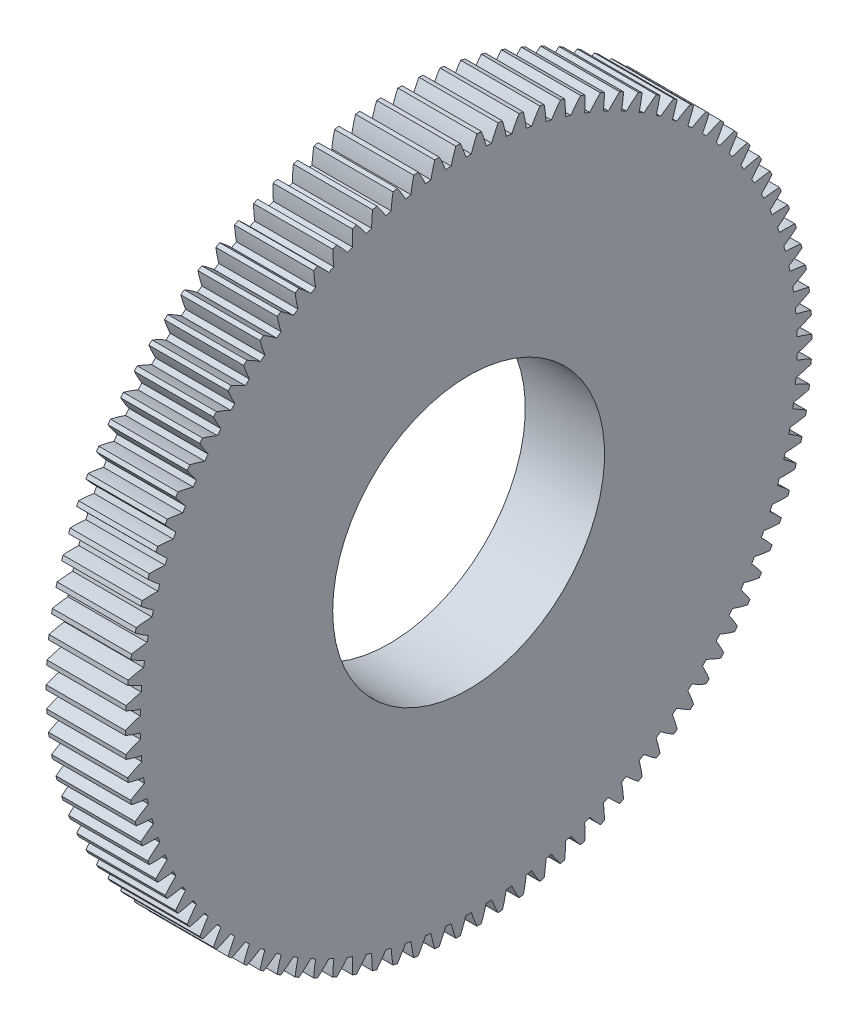
SolidWorks part; units mm, degrees
ref_plane "Plane1" through (0, 0, 0) normal (0, 0, 1) x (1, 0, 0)
ref_plane "Plane2" through (0, 0, 0) normal (0, 1, 0) x (1, 0, 0)
ref_plane "Plane3" through (0, 0, 0) normal (1, 0, 0) x (0, 0, -1)
sketch "HoldingSke" plane through (0, 0, 0) normal (0, 1, 0) x (1, 0, 0)
  line L0 (0, 0) -> (-105.6191, -496.899)
  line L1 (-15, 0) -> (100, 0) construction
  line L2 (0, 0) -> (-2.1039, 2.3779)
  line L3 (0, 0) -> (-11.863, 4.5341)
  line L4 (0, 0) -> (-1.7955, 8.4473)
  line L5 (0, 0) -> (-47.5972, -17.7524)
  line L6 (0, 0) -> (-12.6334, -8.5238)
  line L7 (-2.1039, 2.3779) -> (8.8308, 51.9871)
  line L8 (-76.2, 54.61) -> (-75.184, 54.61)
  line L9 (-71.009, 38.7566) -> (-53.1078, 45.2721)
  line L10 (-76.2, 71.12) -> (104.1128, 71.12)
  line L11 (0, 0) -> (-15.24, 0)
  line L12 (-76.2, 101.6) -> (-76.1492, 101.6)
  line L13 (24.9733, 27.94) -> (52.9518, 28.4284)
  line L14 (24.9733, 27.94) -> (25.0241, 27.9398)
  line L15 (24.9733, 27.94) -> (100.4021, 29.52)
  circle A0 centre (0, 0) radius 0.3969
  circle A1 centre (0, 0) radius 38.1
  circle A2 centre (0, 0) radius 38.1
  circle A3 centre (0, 0) radius 0.3969
  dimension "Num_teeth" = 102
  dimension "H" = 19.05
  dimension "Pitch_radius" = 180.3128
  dimension "Width" = 15.24
  dimension "Thickness" = 15.24
sketch "BasProSke" plane through (0, 0, 0) normal (0, 1, 0) x (1, 0, 0)
  line L0 (-10, 0) -> (60, 0) construction
  line L1 (0, 0) -> (0, 66.04)
  line L2 (0, 0) -> (15.24, 0)
  line L3 (15.24, 0) -> (15.24, 66.04)
  line L4 (15.24, 66.04) -> (0, 66.04)
  dimension "Thickness" = 15.24
  dimension "Diameter" = 132.08
revolve "Base-Revolve" add sketch "BasProSke" angle 360 about L0
sketch "TooCutSke" plane through (0, 0, 0) normal (1, 0, 0) x (0, 0, -1)
  line L1 (0, 0) -> (0, 107) construction
  line L2 (0, 0) -> (-1.0863, 64.7609) construction
  line L3 (0, 0) -> (-3.9888, 129.4658) construction
  line L4 (-1.0863, 64.7609) -> (-1.9944, 64.7329) construction
  arc A0 (0.5348, 63.1929) -> (-0.5348, 63.1929) centre (0, 0) ccw
  arc A1 (1.6252, 66.0454) -> (-1.6252, 66.0454) centre (0, 0) ccw
  circle A2 centre (0, 0) radius 64.77 construction
  circle A3 centre (0, 0) radius 60.8639 construction
  arc A4 (-0.5348, 63.1929) -> (-1.6252, 66.0454) centre (-25.2381, 55.3846) ccw
  arc A5 (1.6252, 66.0454) -> (0.5348, 63.1929) centre (25.2381, 55.3846) ccw
extrude "ToothCut" cut sketch "TooCutSke" along normal through all
fillet "Breaks" [suppressed] radius 0.0254 tangent propagation no
fillet "RootFillets" [suppressed] radius 0.3048
pattern_circular "TeethCuts" count 102 every 3.529 about axis through (-10, 0, 0) along (1, 0, 0) of "ToothCut", "RootFillets", "Breaks"
sketch "HubNeaOneSke" plane through (0, 0, 0) normal (-1, 0, 0) x (0, 0, 1)
  circle A0 centre (0, 0) radius 38.1
  dimension "Diameter" = 76.2
extrude "HubNearOne" [suppressed] add sketch "HubNeaOneSke" along normal blind 35.5601
sketch "HubNeaBotSke" plane through (0, 0, 0) normal (-1, 0, 0) x (0, 0, 1)
  circle A0 centre (0, 0) radius 38.1
  dimension "Diameter" = 76.2
extrude "HubNearBoth" [suppressed] add sketch "HubNeaBotSke" along normal blind 17.78
ref_plane "FarPln" through (15.24, 0, 0) normal (1, 0, 0) x (0, 0, -1)
sketch "HubFarSke" plane through (15.24, 0, 0) normal (1, 0, 0) x (0, 0, -1)
  circle A0 centre (0, 0) radius 38.1
  dimension "Diameter" = 76.2
extrude "HubFar" [suppressed] add sketch "HubFarSke" along normal blind 17.78
sketch "BorSke" plane through (0, 0, 0) normal (1, 0, 0) x (0, 0, -1)
  circle A0 centre (0, 0) radius 0.3969
  dimension "Diameter" = 0.7937
extrude "Bore" cut sketch "BorSke" along normal mid plane 101.6001
sketch "KeySke" plane through (0, 0, 0) normal (1, 0, 0) x (0, 0, -1)
  line L0 (-0.127, 0) -> (-0.127, 0.6191)
  line L1 (-0.127, 0.6191) -> (0.127, 0.6191)
  line L2 (0.127, 0.6191) -> (0.127, 0)
  line L3 (0, 0) -> (0, 34) construction
  line L4 (-0.127, 0) -> (0.127, 0)
  dimension "Width" = 0.254
extrude "Keyway" [suppressed] cut sketch "KeySke" along normal mid plane 101.6001
pattern_circular "Keyway2" [suppressed] count 2 every 90 about axis through (-10, 0, 0) along (1, 0, 0) reverse direction yes
sketch "Sketch1" plane through (0, 0, 0) normal (-1, 0, 0) x (0, 0, 1)
  circle A0 centre (0, 0.3969) radius 26.1531
  circle A1 centre (0, 0) radius 0.3969 construction
extrude "Cut-Extrude1" cut sketch "Sketch1" against normal through all
equation "' \"Pitch@HoldingSke\" = 4"
equation "' \"Num_teeth@HoldingSke\" = 12"
equation "' \"Ap@HoldingSke\" =  20"
equation "' \"Ap@HoldingSke\" = 20"
equation "' \"Width@HoldingSke\" = 0.5"
equation "' \"Hub_dia@HoldingSke\"= 1"
equation "' \"Hub_dia@HoldingSke\" = 1"
equation "' \"Overall_len@HoldingSke\" = 1.0"
equation "' \"Bore@HoldingSke\" = 0.75"
equation "' \"T_dim@HoldingSke\" = 0.85"
equation "' \"Width@KeySke\" = 0.25"
equation "' \"Show_teeth@HoldingSke\" = 13"
equation "' \"Backlash@HoldingSke\" = 0.009"
equation "' \"Addendum_fac@HoldingSke\" = 1.0"
equation "' \"Dedendum_fac@HoldingSke\" = 1.25"
equation "' \"Dedendum_add@HoldingSke\" = 0.00005"
equation "' \"Clearance_fac@HoldingSke\" = 0.25"
equation "' \"Pitch@HoldingSke\" = 0.5"
equation "' \"Num_teeth@HoldingSke\" = 23"
equation "' \"Show_teeth@HoldingSke\" = 23"
equation "' \"Backlash@HoldingSke\" = 0.0375"
equation "\"Overcut_dia@TooCutSke\" = (\"Num_teeth@HoldingSke\" + 2 * \"Addendum_fac@HoldingSke\") / \"Pitch@HoldingSke\" + 0.002"
equation "\"Pitch_dia@TooCutSke\" = \"Num_teeth@HoldingSke\" / \"Pitch@HoldingSke\""
equation "\"Base_dia@TooCutSke\" = \"Num_teeth@HoldingSke\" / \"Pitch@HoldingSke\" * cos((\"Ap@HoldingSke\"  * 3.14159265 / 180))"
equation "\"Root_dia@TooCutSke\" = (\"Num_teeth@HoldingSke\" + 2) / \"Pitch@HoldingSke\" - 2 * (\"Addendum_fac@HoldingSke\" + \"Dedendum_fac@HoldingSke\") / \"Pitch@HoldingSke\" - \"Dedendum_add@HoldingSke\" * 2"
equation "\"Half_ang@TooCutSke\" = 180 / \"Num_teeth@HoldingSke\""
equation "\"Half_CT@TooCutSke\" = \"Num_teeth@HoldingSke\" / \"Pitch@HoldingSke\" * sin((3.14159265 / 2 / \"Num_teeth@HoldingSke\")) / 2 - 7 * \"Backlash@HoldingSke\" / 4"
equation "\"Flank_rad@TooCutSke\" = \"Num_teeth@HoldingSke\" / \"Pitch@HoldingSke\" / 5"
equation "\"Radius@RootFillets\" = \"Clearance_fac@HoldingSke\" / \"Pitch@HoldingSke\" + \"Dedendum_add@HoldingSke\""
equation "\"Break_rad@Breaks\" = 0.02 / \"Pitch@HoldingSke\""
equation "\"Thickness@HoldingSke\" = \"Width@HoldingSke\""
equation "\"OAL@HoldingSke\" = \"Thickness@HoldingSke\""
equation "\"MHD@HoldingSke\" = (\"Num_teeth@HoldingSke\" + 2) / \"Pitch@HoldingSke\" - 2 * (\"Addendum_fac@HoldingSke\" + \"Dedendum_fac@HoldingSke\")  / \"Pitch@HoldingSke\" - \"Dedendum_add@HoldingSke\" * 2"
equation "\"MBD@HoldingSke\" = (\"Num_teeth@HoldingSke\" + 2) / \"Pitch@HoldingSke\" - 2 * (\"Addendum_fac@HoldingSke\" + \"Dedendum_fac@HoldingSke\")  / \"Pitch@HoldingSke\" - \"Dedendum_add@HoldingSke\" * 2 - 0.002"
equation "\"MHD@HoldingSke\" = ((sgn( \"MHD@HoldingSke\" - \"Hub_dia@HoldingSke\" )-1)*( \"MHD@HoldingSke\" - \"Hub_dia@HoldingSke\" ))/-2+ \"Hub_dia@HoldingSke\""
equation "\"MBD@HoldingSke\" = ((sgn( \"MBD@HoldingSke\" - \"Bore@HoldingSke\" )-1)*( \"MBD@HoldingSke\" - \"Bore@HoldingSke\" ))/-2+ \"Bore@HoldingSke\""
equation "\"OAL@HoldingSke\" = ((sgn( \"OAL@HoldingSke\" - \"Overall_len@HoldingSke\" )+1)*( \"OAL@HoldingSke\" - \"Overall_len@HoldingSke\" ))/2 + \"Overall_len@HoldingSke\" + 0.000002"
equation "\"Num_teeth@TeethCuts\" = int( \"Show_teeth@HoldingSke\" ) + 1"
equation "\"Num_teeth@TeethCuts\" = ((sgn( \"Num_teeth@TeethCuts\" - \"Num_teeth@HoldingSke\" )-1)*( \"Num_teeth@TeethCuts\" - \"Num_teeth@HoldingSke\" ))/-2+ \"Num_teeth@HoldingSke\""
equation "\"Num_teeth@TeethCuts\" = ((sgn( \"Num_teeth@TeethCuts\" - 2.0)+1)*( \"Num_teeth@TeethCuts\" - 2.0))/2 +2.0"
equation "\"Angle@TeethCuts\" = 360.0 / \"Num_teeth@HoldingSke\""
equation "\"Diameter@BasProSke\" = (\"Num_teeth@HoldingSke\" + 2 * \"Addendum_fac@HoldingSke\") / \"Pitch@HoldingSke\""
equation "\"Thickness@BasProSke\"  = \"Thickness@HoldingSke\""
equation "' \"Fillet_rad@BasProSke\" =  \"Thickness@HoldingSke\" * 0.05"
equation "' \"Fillet_rad@BasProSke\" = \"Thickness@HoldingSke\" * 0.05"
equation "\"MHD@HoldingSke\" = ((sgn( \"MHD@HoldingSke\" - \"Root_dia@TooCutSke\" )-1)*( \"MHD@HoldingSke\" - \"Root_dia@TooCutSke\" ))/-2+ \"Root_dia@TooCutSke\""
equation "\"Diameter@HubNeaOneSke\" = \"MHD@HoldingSke\""
equation "\"Length@HubNearOne\" = \"OAL@HoldingSke\" - \"Thickness@BasProSke\""
equation "\"Diameter@HubNeaBotSke\" = \"MHD@HoldingSke\""
equation "\"Length@HubNearBoth\" = ( \"OAL@HoldingSke\" - \"Thickness@BasProSke\" ) / 2.0"
equation "\"Thickness@FarPln\" = \"Thickness@BasProSke\""
equation "\"Diameter@HubFarSke\" = \"MHD@HoldingSke\""
equation "\"Length@HubFar\" = ( \"OAL@HoldingSke\" - \"Thickness@BasProSke\" ) / 2.0"
equation "\"Diameter@BorSke\" = \"MBD@HoldingSke\""
equation "\"D1@Bore\" = \"OAL@HoldingSke\" * 2.0"
equation "\"D1@Keyway\" = \"OAL@HoldingSke\" * 2.0"
equation "\"Offset@KeySke\" = \"T_dim@HoldingSke\" - \"MBD@HoldingSke\" / 2.0"
